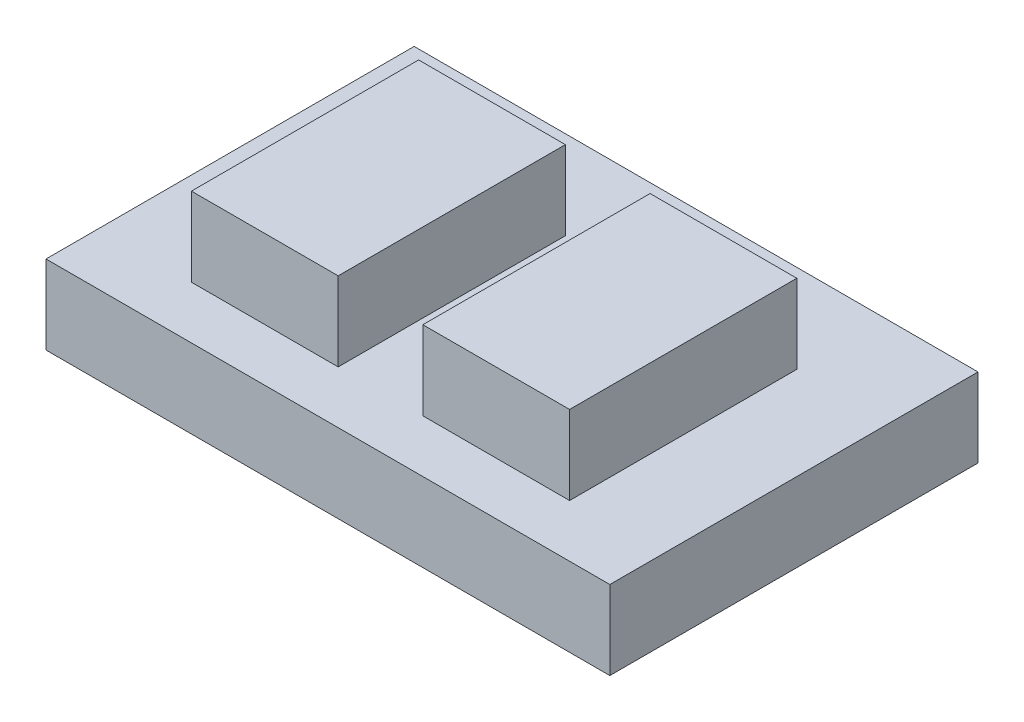
SolidWorks part; units mm, degrees
ref_plane "Front Plane" through (0, 0, 0) normal (0, 0, 1) x (1, 0, 0)
ref_plane "Top Plane" through (0, 0, 0) normal (0, 1, 0) x (1, 0, 0)
ref_plane "Right Plane" through (0, 0, 0) normal (1, 0, 0) x (0, 0, -1)
sketch "Sketch1" plane through (0, 0, 0) normal (0, 1, 0) x (1, 0, 0)
  line L0 (-6.3611, 2.6026) -> (-6.3611, -4.3974)
  line L1 (-6.3611, 2.6026) -> (4.3589, 2.6026)
  line L2 (-6.3611, -4.3974) -> (4.3589, -4.3974)
  line L3 (4.3589, 2.6026) -> (4.3589, -4.3974)
  dimension "D1" = 7
  dimension "D2" = 10.72
extrude "Boss-Extrude1" add sketch "Sketch1" along normal blind 1.5
sketch "Sketch2" plane through (0, 1.5, 0) normal (0, 1, 0) x (1, 0, 0)
  line L0 (-4.5961, 0.9226) -> (-4.5961, -3.3974)
  line L1 (-4.5961, 0.9226) -> (-1.8061, 0.9226)
  line L2 (-4.5961, -3.3974) -> (-1.8061, -3.3974)
  line L3 (-1.8061, 0.9226) -> (-1.8061, -3.3974)
  line L4 (-0.1961, 0.9226) -> (-0.1961, -3.3974)
  line L5 (-0.1961, 0.9226) -> (2.5939, 0.9226)
  line L6 (-0.1961, -3.3974) -> (2.5939, -3.3974)
  line L7 (2.5939, 0.9226) -> (2.5939, -3.3974)
  line L8 (-3.2011, -3.3974) -> (1.1989, -3.3974) construction
  line L9 (-6.3611, -4.3974) -> (4.3589, -4.3974) construction
  line L10 (-1.0011, -4.3974) -> (-1.0011, -3.3974) construction
  dimension "D1" = 4.32
  dimension "D2" = 2.79
  dimension "D3" = 4.4
  dimension "D4" = 1
extrude "Boss-Extrude2" add sketch "Sketch2" along normal blind 1.5
